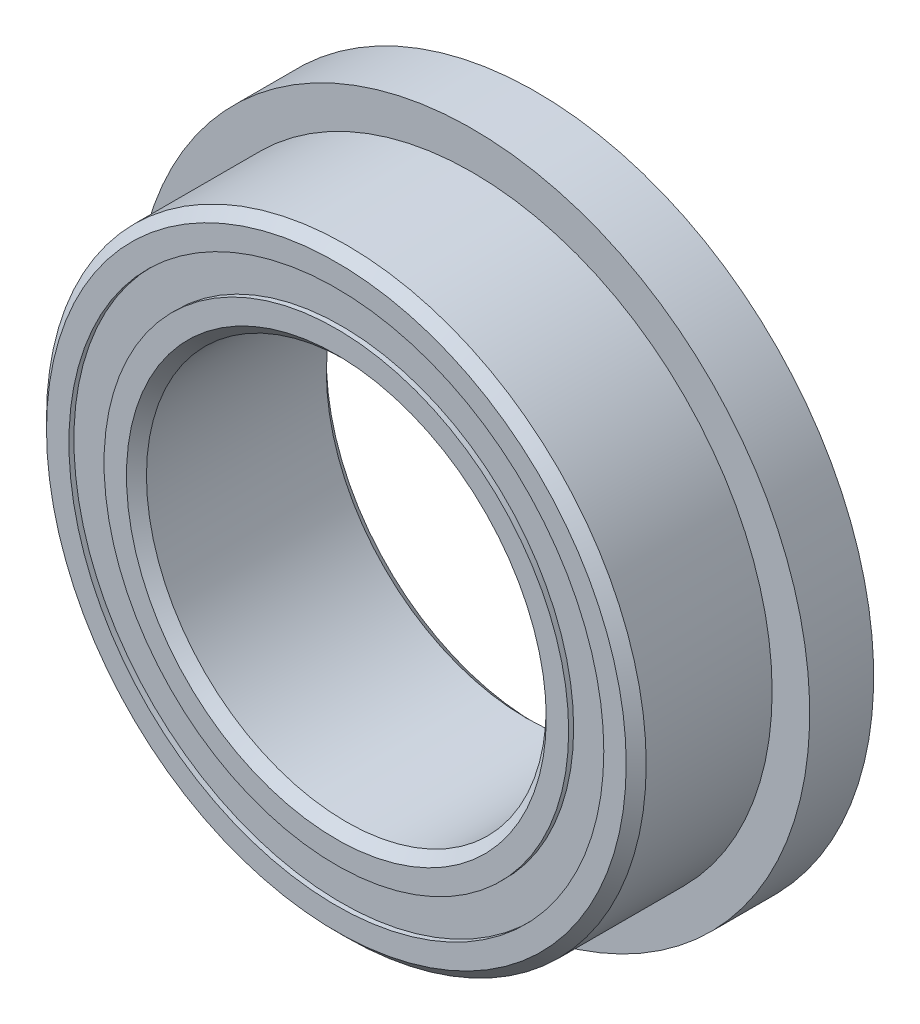
SolidWorks part; units mm, degrees
ref_plane "Front Plane" through (0, 0, 0) normal (0, 0, 1) x (1, 0, 0)
ref_plane "Top Plane" through (0, 0, 0) normal (0, 1, 0) x (1, 0, 0)
ref_plane "Right Plane" through (0, 0, 0) normal (1, 0, 0) x (0, 0, -1)
sketch "Sketch1" plane through (0, 0, 0) normal (1, 0, 0) x (0, 0, -1)
  line L0 (-1.5875, 0) -> (1.5875, 0) construction
  line L1 (0, 4.7625) -> (0, -4.7625) construction
  line L2 (1.5875, 4.7625) -> (-1.5875, 4.7625) construction
  line L9 (0, 4.7625) -> (0, 3.9688) construction
  line L10 (0, 3.9688) -> (0, 3.175) construction
  point P14 (0, 3.175)
  dimension "Width" = 3.175
  dimension "OD" = 9.525
  dimension "Shaft Dia" = 6.35
sketch "Sketch2" plane through (0, 0, 0) normal (1, 0, 0) x (0, 0, -1)
  line L0 (1.9844, 0) -> (-1.9844, 0) construction
  line L1 (1.5875, 4.2479) -> (0.5715, 4.2479) construction
  line L2 (1.5875, 4.2479) -> (1.5875, 5.3594) construction
  line L3 (1.5875, 5.3594) -> (0.5715, 5.3594) construction
  line L4 (0.5715, 4.2479) -> (0.5715, 5.3594) construction
  dimension "Th" = 1.016
  dimension "Flange OD" = 10.7188
  dimension "D1" = 0.2791
sketch "Sketch" plane through (0, 0, 0) normal (1, 0, 0) x (0, 0, -1)
  line L0 (-1.5875, 0) -> (1.5875, 0) construction
  line L1 (0, 4.7625) -> (0, -4.7625) construction
  line L2 (1.4287, 4.7625) -> (-1.4287, 4.7625)
  line L3 (-1.4287, 4.7625) -> (-1.5875, 4.6037)
  line L4 (-1.5875, 4.6037) -> (-1.5875, 4.2479)
  line L5 (-1.5875, 4.2479) -> (-0.7056, 4.2479)
  line L6 (1.5875, 4.2479) -> (0.7056, 4.2479)
  line L7 (1.5875, 4.6037) -> (1.5875, 4.2479)
  line L8 (1.4287, 4.7625) -> (1.5875, 4.6037)
  line L9 (0, 4.7625) -> (0, 3.9688) construction
  line L10 (0, 3.9688) -> (0, 3.175) construction
  arc A0 (-0.7056, 4.2479) -> (0.7056, 4.2479) centre (0, 3.9688) cw
  point P14 (0, 3.175)
  dimension "D1" = 45
  dimension "D2" = 0.1588
  dimension "D3" = 1.4111
  dimension "D4" = 0.2791
revolve "Revolve1" add sketch "Sketch" angle 360 about L0
sketch "Sketch3" plane through (0, 0, 0) normal (1, 0, 0) x (0, 0, -1)
  line L0 (-1.5875, 3.6896) -> (-0.7056, 3.6896)
  line L1 (0, 4.7625) -> (0, -4.7625) construction
  line L2 (-1.5875, 4.6037) -> (-1.5875, 4.2479) construction
  line L3 (-1.5875, 3.6896) -> (-1.5875, 3.3337)
  line L4 (-1.4287, 4.7625) -> (-1.5875, 4.6037) construction
  line L5 (-1.5875, 3.3337) -> (-1.4288, 3.175)
  line L6 (-1.4288, 3.175) -> (1.4287, 3.175)
  line L7 (1.4287, 4.7625) -> (1.4287, -4.7625) construction
  line L8 (1.4287, 3.175) -> (1.5875, 3.3337)
  line L9 (1.5875, -4.6037) -> (1.5875, 4.6037) construction
  line L10 (1.5875, 3.3337) -> (1.5875, 3.6896)
  line L11 (1.5875, 3.6896) -> (0.7056, 3.6896)
  line L13 (1.4287, 4.7625) -> (1.5875, 4.6037) construction
  arc A0 (0.7056, 4.2479) -> (-0.7056, 4.2479) centre (0, 3.9688) ccw construction
  arc A1 (0.7056, 3.6896) -> (-0.7056, 3.6896) centre (0, 3.9687) cw
revolve "Revolve3" add sketch "Sketch3" angle 360 about L0
sketch "Sketch4" plane through (0, 0, 0) normal (1, 0, 0) x (0, 0, -1)
  line L0 (-0.7588, 3.9688) -> (0.7588, 3.9688)
  arc A2 (-0.7588, 3.9688) -> (0.7588, 3.9688) centre (0, 3.9688) cw
  arc A3 (0.7056, 4.2479) -> (-0.7056, 4.2479) centre (0, 3.9688) ccw construction
revolve "Revolve4" add sketch "Sketch4" angle 360 about L0
ref_axis "Axis1" through (0, 0, -1.5875) along (0, 0, 1)
pattern_circular "CirPattern1" count 14 every 25.714 about axis through (0, 0, -1.5875) along (0, 0, 1) of bodies 104
sketch "Sketch5" plane through (0, 0, 0) normal (1, 0, 0) x (0, 0, -1)
  line L0 (-1.5875, 4.2479) -> (-0.7056, 4.2479) construction
  line L1 (-1.5081, 4.2479) -> (-0.7588, 4.2479)
  line L2 (-1.5081, 4.2479) -> (-1.5081, 3.6896)
  line L3 (-1.5081, 3.6896) -> (-0.7588, 3.6896)
  line L4 (-0.7588, 4.2479) -> (-0.7588, 3.6896)
  line L5 (-1.5875, 3.6896) -> (-0.7056, 3.6896) construction
  line L6 (1.5875, 4.2479) -> (0.7056, 4.2479) construction
  line L7 (1.5081, 4.2479) -> (0.7588, 4.2479)
  line L8 (1.5081, 4.2479) -> (1.5081, 3.6896)
  line L9 (1.5081, 3.6896) -> (0.7588, 3.6896)
  line L10 (0.7588, 4.2479) -> (0.7588, 3.6896)
  line L11 (1.5875, 3.6896) -> (0.7056, 3.6896) construction
  line L12 (-1.4287, 4.7625) -> (-1.5875, 4.6037) construction
  point P18 (-1.5081, 4.6831)
revolve "Revolve5" add sketch "Sketch5" angle 360 about L0
sketch "Sketch6" plane through (0, 0, 0) normal (1, 0, 0) x (0, 0, -1)
  line L0 (1.5875, 0) -> (-1.5875, 0) construction
  line L1 (1.5875, 4.2479) -> (0.5715, 4.2479)
  line L2 (1.5875, 4.2479) -> (1.5875, 5.3594)
  line L3 (1.5875, 5.3594) -> (0.5715, 5.3594)
  line L4 (0.5715, 4.2479) -> (0.5715, 5.3594)
  dimension "Th" = 1.016
  dimension "Flange OD" = 10.7188
revolve "Revolve6" add sketch "Sketch6" angle 360 about L0
sketch "Sketch7" plane through (0, 0, 0) normal (1, 0, 0) x (0, 0, -1)
  line L1 (1.5875, 4.7625) -> (-1.5875, 4.7625) construction
  line L2 (1.5875, 4.7625) -> (-1.5875, 4.7625) construction
  line L3 (1.5875, -4.7625) -> (-1.5875, -4.7625) construction
  line L4 (1.5875, -5.3594) -> (1.5875, 5.3594) construction
  line L5 (1.5875, 4.7625) -> (1.5875, 5.3594) construction
  line L6 (1.5875, 5.3594) -> (0.5715, 5.3594) construction
  dimension "D1" = 9.525
  dimension "D2" = 3.175
sketch "Sketch8" plane through (0, 0, 0) normal (0, 0, 1) x (1, 0, 0)
  circle A0 centre (0, 0) radius 3.175 construction
  dimension "D1" = 6.35
equation "\"D2@Sketch\" = \"Width@Sketch1\" * .05"
equation "\"D3@Sketch\" = \"Width@Sketch1\" / 2.25"
equation "\"D4@Sketch\"=(  (  ( \"OD@Sketch1\" - \"Width@Sketch1\" )  / 2 )  / 3.25 )  / 3.5"
equation "\"D2@CirPattern1\" = 360/\"Balls@CirPattern1\""
equation "\"D1@Sketch2\"=(  (  ( \"OD@Sketch1\" - \"Width@Sketch1\" )  / 2 )  / 3.25 )  / 3.5"
